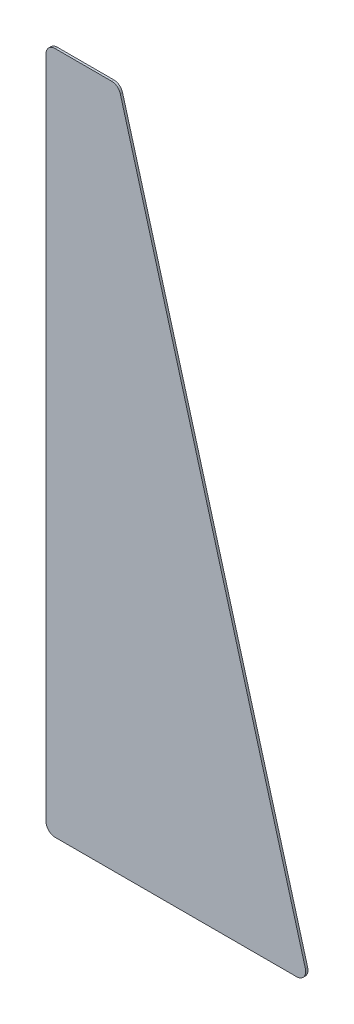
SolidWorks part; units mm, degrees
material "PC High Viscosity"
ref_plane "Front Plane" through (0, 0, 0) normal (0, 0, 1) x (1, 0, 0)
ref_plane "Top Plane" through (0, 0, 0) normal (0, 1, 0) x (1, 0, 0)
ref_plane "Right Plane" through (0, 0, 0) normal (1, 0, 0) x (0, 0, -1)
sketch "Sketch2" plane through (0, 0, 0) normal (0, 0, 1) x (1, 0, 0)
  line L0 (0, 0) -> (0, 479.171)
  line L5 (184.15, 0) -> (0, 0)
  line L6 (0, 479.171) -> (50.8, 479.171)
  line L7 (50.8, 479.171) -> (184.15, 0)
  dimension "D1" = 479.171
  dimension "D2" = 184.15
  dimension "D5" = 50.8
extrude "Boss-Extrude1" add sketch "Sketch2" along normal blind 1.5875
fillet "Fillet1" radius 6.35 4 edges at (0, 0, 0.7937) (50.8, 479.171, 0.7937) (0, 479.171, 0.7937) (184.15, 0, 0.7937)
